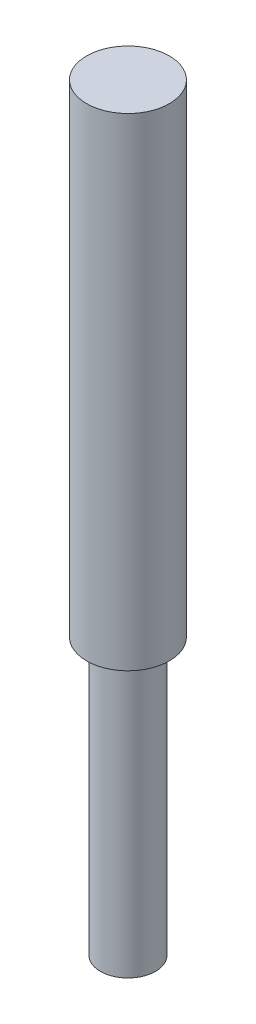
SolidWorks part; units mm, degrees
ref_plane "Front Plane" through (0, 0, 0) normal (0, 0, 1) x (1, 0, 0)
ref_plane "Top Plane" through (0, 0, 0) normal (0, 1, 0) x (1, 0, 0)
ref_plane "Right Plane" through (0, 0, 0) normal (1, 0, 0) x (0, 0, -1)
sketch "Sketch1" plane through (0, 0, 0) normal (0, 1, 0) x (1, 0, 0)
  circle A0 centre (0, 0) radius 3
  circle A1 centre (0, 0) radius 2
  dimension "D1" = 6
  dimension "D2" = 1
extrude "Boss-Extrude1" add sketch "Sketch1" along normal blind 35 contours A0 | A1 A0 | A0 | A1 region at (-2.9151, 0, 0) region at (0, 0, 0)
extrude "Boss-Extrude2" add sketch "Sketch1<3>" against normal blind 20 contours A1 region at (0, 0, 0)
sketch "Sketch1<3>" plane through (0, 0, 0) normal (0, 1, 0) x (1, 0, 0) same geometry as "Sketch1"
